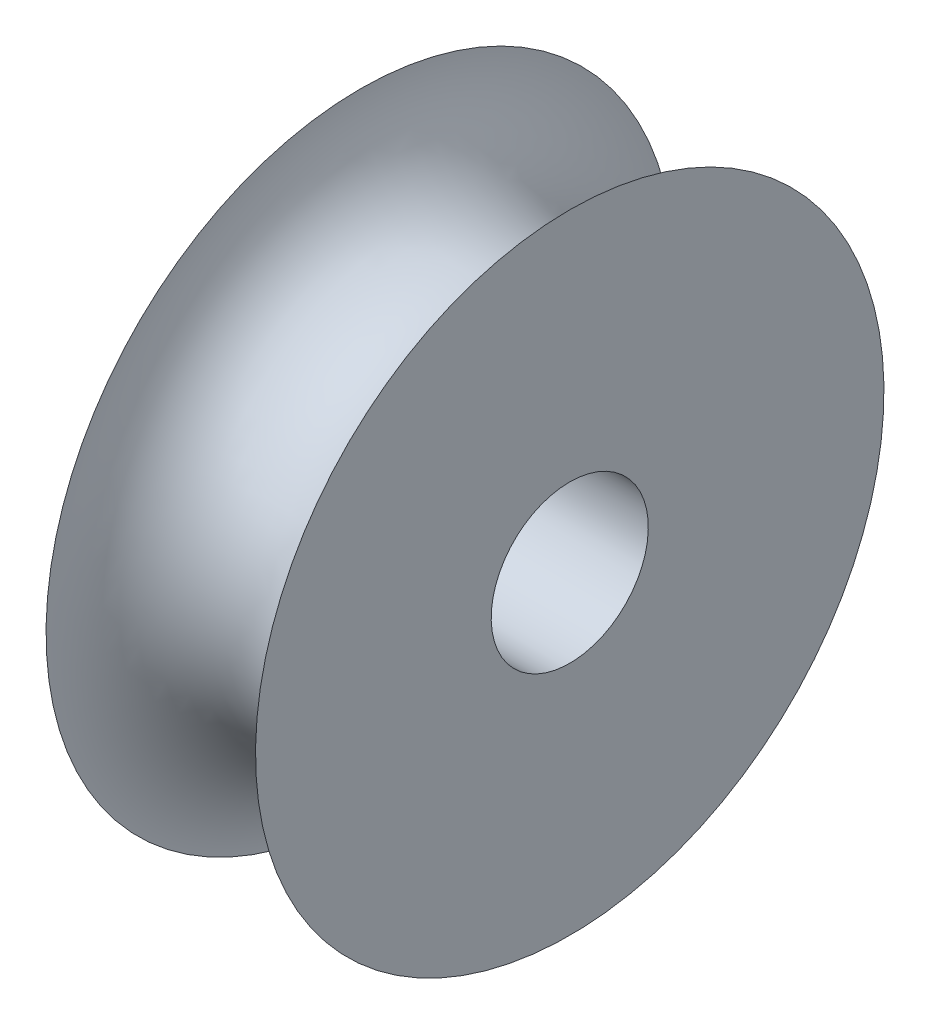
SolidWorks part; units mm, degrees
ref_plane "Ebene vorne" through (0, 0, 0) normal (0, 0, 1) x (1, 0, 0)
ref_plane "Ebene oben" through (0, 0, 0) normal (0, 1, 0) x (1, 0, 0)
ref_plane "Ebene rechts" through (0, 0, 0) normal (1, 0, 0) x (0, 0, -1)
sketch "Skizze1" plane through (0, 0, 0) normal (0, 0, 1) x (1, 0, 0)
  line L0 (0, 0) -> (-4, 0)
  line L1 (-4, 0) -> (-4, 6)
  line L2 (0, 0) -> (0, 6)
  arc A0 (-4, 6) -> (0, 6) centre (-2, 6) ccw
revolve "Rotation1" add sketch "Skizze1" angle 360 about L0
sketch "Skizze2" plane through (0, 0, 0) normal (1, 0, 0) x (0, 0, -1)
  circle A0 centre (0, 0) radius 1.5
extrude "Schnitt-Linear austragen1" cut sketch "Skizze2" against normal blind 10
